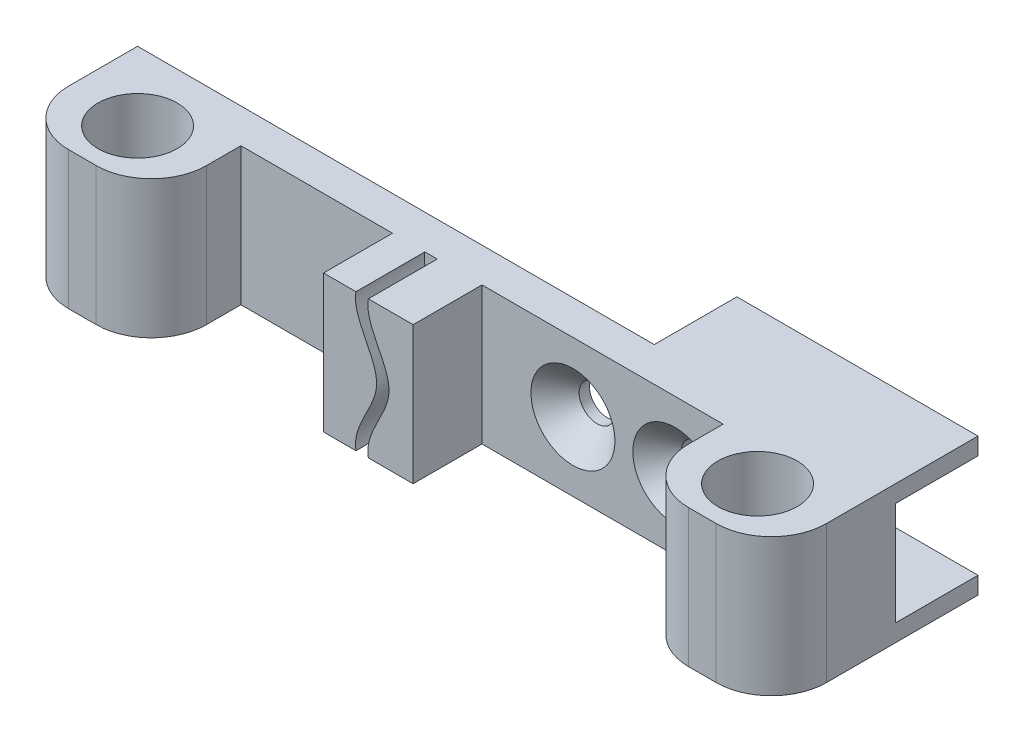
SolidWorks part; units mm, degrees
ref_plane "Plan de face" through (0, 0, 0) normal (0, 0, 1) x (1, 0, 0)
ref_plane "Plan de dessus" through (0, 0, 0) normal (0, 1, 0) x (1, 0, 0)
ref_plane "Plan de droite" through (0, 0, 0) normal (1, 0, 0) x (0, 0, -1)
sketch "Esquisse1" plane through (0, 0, 0) normal (0, 1, 0) x (1, 0, 0)
  line L0 (47, -18) -> (43, -18)
  line L1 (-55, 0) -> (55, 0)
  line L4 (55, 0) -> (55, -10)
  line L5 (35, -10) -> (35, -5)
  line L6 (35, -5) -> (-35, -5)
  line L7 (0, 0) -> (0, -5) construction
  line L8 (-35, -10) -> (-35, -5)
  line L9 (-55, 0) -> (-55, -10)
  line L10 (-47, -18) -> (-43, -18)
  circle A0 centre (45, -10) radius 5.75
  circle A1 centre (-45, -10) radius 5.75
  arc A2 (43, -18) -> (35, -10) centre (43, -10) cw
  arc A3 (47, -18) -> (55, -10) centre (47, -10) ccw
  arc A4 (-55, -10) -> (-47, -18) centre (-47, -10) ccw
  arc A5 (-35, -10) -> (-43, -18) centre (-43, -10) cw
  point P17 (35, -18)
  point P20 (55, -18)
  point P21 (45, -8.6459)
  point P24 (-55, -18)
  point P27 (-35, -18)
  dimension "D3" = 11.5
  dimension "D8" = 8
  dimension "D10" = 8
  dimension "D1" = 55
  dimension "D2" = 45
  dimension "D4" = 18
  dimension "D5" = 5
  dimension "D6" = 10
  dimension "D7" = 10
  dimension "D9" = 10
extrude "Boss.-Extru.1" add sketch "Esquisse1" along normal blind 20
sketch "Esquisse2" plane through (0, 0, 0) normal (0, 0, -1) x (-1, 0, 0)
  line L1 (-55, 20) -> (-20, 20)
  line L2 (-55, 20) -> (-55, 17.5)
  line L3 (-55, 17.5) -> (-20, 17.5)
  line L4 (-20, 20) -> (-20, 17.5)
  line L5 (-55, 0) -> (-20, 0)
  line L6 (-55, 0) -> (-55, 2.5)
  line L7 (-55, 2.5) -> (-20, 2.5)
  line L8 (-20, 0) -> (-20, 2.5)
  dimension "D1" = 15
  dimension "D2" = 20
  dimension "D3" = 2.5
  dimension "D4" = 35
extrude "Boss.-Extru.2" add sketch "Esquisse2" along normal blind 12
sketch "Esquisse3" plane through (0, 0, 0) normal (0, 0, -1) x (-1, 0, 0)
  line L0 (-55, 10) -> (55, 10) construction
  line L1 (-55, 17.5) -> (-55, 2.5) construction
  line L2 (55, 20) -> (55, 0) construction
  circle A0 centre (-13.2, 10) radius 2.6
  circle A1 centre (-28, 10) radius 2.6
  dimension "D1" = 5.2
  dimension "D2" = 5.2
  dimension "D3" = 14.8
  dimension "D4" = 27
extrude "Enlèv. mat.-Extru.1" cut sketch "Esquisse3" against normal blind 22
chamfer "Chanfrein1" distance 3.5 angle 45 2 edges at (25.4, 10, 5) (10.6, 10, 5)
sketch "Esquisse4" plane through (0, 0, 0) normal (1, 0, 0) x (0, 0, -1)
  line L1 (-5, 20) -> (-15, 20)
  line L2 (-5, 20) -> (-5, 0)
  line L3 (-5, 0) -> (-15, 0)
  line L4 (-15, 20) -> (-15, 0)
  point P4 (0, 0)
  point P5 (-2.6513, 17.7373)
  dimension "D1" = 10
extrude "Boss.-Extru.3" add sketch "Esquisse4" against normal blind 13
sketch "Esquisse7" plane through (0, 0, 15) normal (0, 0, 1) x (1, 0, 0)
  line L0 (-13, 20) -> (0, 20) construction
  line L1 (-13, 0) -> (0, 0) construction
  line L2 (0, 10) -> (-13, 10) construction
  line L3 (0, 0) -> (0, 20) construction
  line L4 (-13, 0) -> (-13, 20) construction
  line L5 (0, 20) -> (0, 0) construction
  line L6 (-8.3, 20) -> (-6.5, 20)
  line L7 (-6.5, 0) -> (-8.3, 0)
  spline S0 degree 3 poles (-6.5, 20) (-7.109, 16.5897) (0.109, 10) (-7.109, 3.4103) (-6.5, 0) knots 0 0 0 0 0.5 1 1 1 1
  spline S1 degree 3 poles (-8.3, 20) (-8.909, 16.5897) (-1.691, 10) (-8.909, 3.4103) (-8.3, 0) knots 0 0 0 0 0.5 1 1 1 1
  dimension "D1" = 1.8
  dimension "D2" = 1.8
  dimension "D3" = 1.8
  dimension "D4" = 1.8
  dimension "D5" = 1.8
  dimension "D6" = 4.5
  dimension "D7" = 4.5
  dimension "D8" = 3.5
  dimension "D9" = 5
  dimension "D10" = 5
extrude "Enlèv. mat.-Extru.2" cut sketch "Esquisse7" against normal blind 10
equation "\"D7@Esquisse1\"=\"D6@Esquisse1\""
equation "\"D9@Esquisse1\"=\"D6@Esquisse1\""
equation "\"D3@Esquisse2\"=(\"D2@Esquisse2\"-\"D1@Esquisse2\")/2"
equation "\"D2@Esquisse3\"=\"D1@Esquisse3\""
equation "\"D3@Esquisse3\"=19-4.2"
equation "\"D3@Esquisse7\"=\"D1@Esquisse7\""
equation "\"D2@Esquisse7\"=\"D1@Esquisse7\""
equation "\"D4@Esquisse7\"=\"D1@Esquisse7\""
equation "\"D5@Esquisse7\"=\"D1@Esquisse7\""
